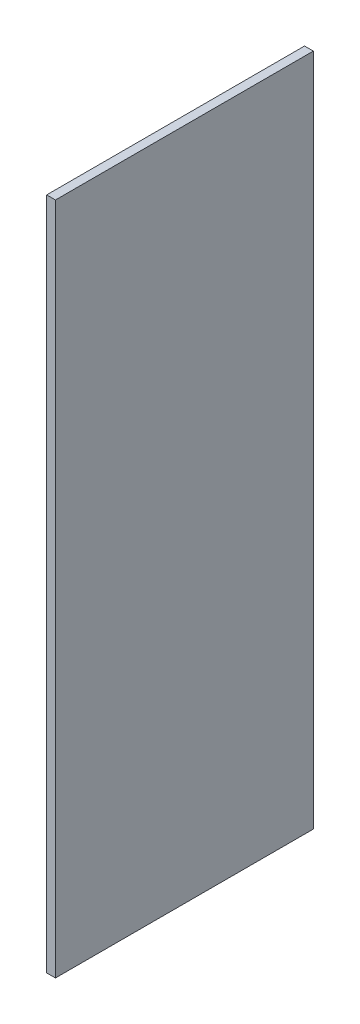
SolidWorks part; units mm, degrees
ref_plane "Front Plane" through (0, 0, 0) normal (0, 0, 1) x (1, 0, 0)
ref_plane "Top Plane" through (0, 0, 0) normal (0, 1, 0) x (1, 0, 0)
ref_plane "Right Plane" through (0, 0, 0) normal (1, 0, 0) x (0, 0, -1)
sketch "Sketch1" plane through (0, 0, 0) normal (0, 0, 1) x (1, 0, 0)
  line L0 (-108.5345, -3.9032) -> (-108.5345, 1456.1455)
  line L1 (-89.4845, -3.9032) -> (-89.4845, 1456.1455)
  line L2 (-108.5345, -3.9032) -> (-89.4845, -3.9032)
  line L3 (-108.5345, 1456.1455) -> (-89.4845, 1456.1455)
  dimension "D1" = 19.05
extrude "Boss-Extrude1" add sketch "Sketch1" along normal blind 558.8
